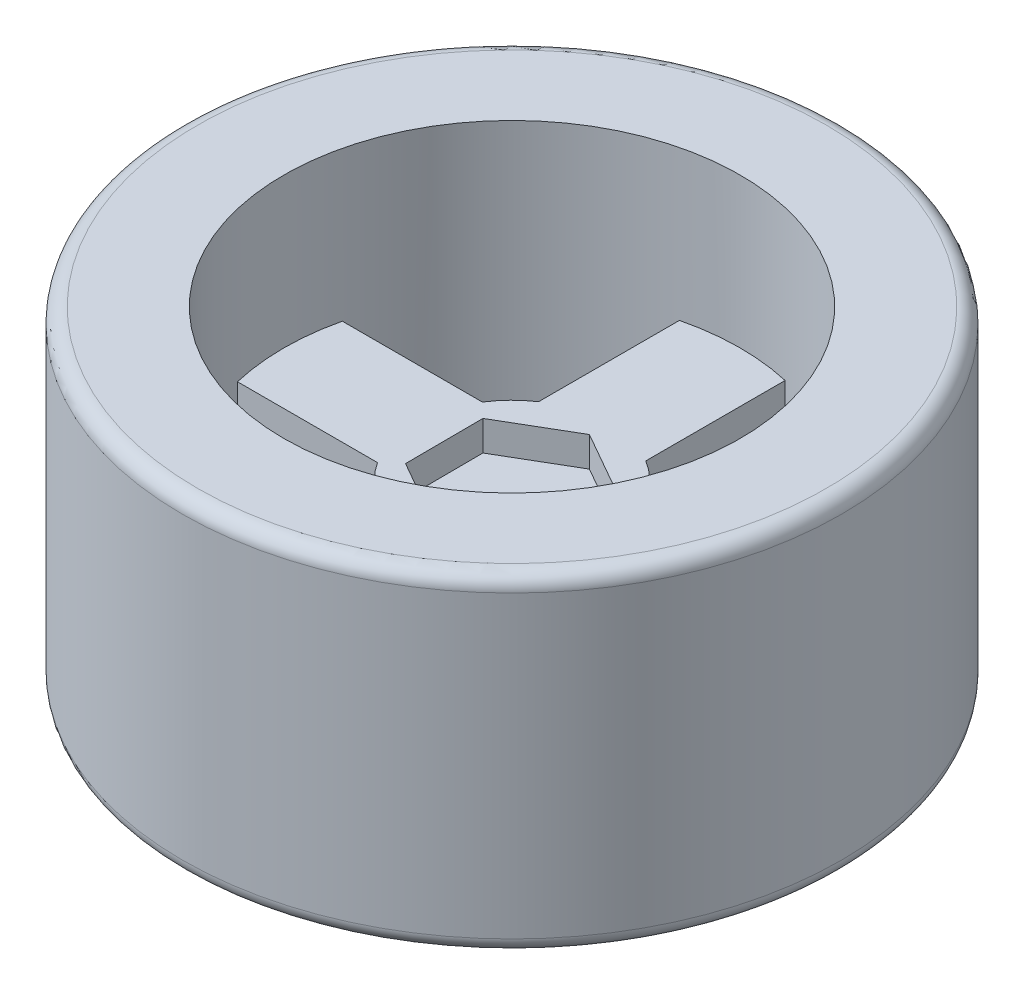
SolidWorks part; units mm, degrees
ref_plane "Front Plane" through (0, 0, 0) normal (0, 0, 1) x (1, 0, 0)
ref_plane "Top Plane" through (0, 0, 0) normal (0, 1, 0) x (1, 0, 0)
ref_plane "Right Plane" through (0, 0, 0) normal (1, 0, 0) x (0, 0, -1)
sketch "Sketch1" plane through (0, 0, 0) normal (0, 1, 0) x (1, 0, 0)
  line L0 (-3.4277, 8.3858) -> (-3.4277, 17.6894)
  line L1 (-14.8781, 6.3326) -> (-5.5267, 6.3326)
  line L3 (-14.8781, -0.6674) -> (-5.5267, -0.6674)
  line L18 (3.5723, 8.2301) -> (3.5723, 17.6319)
  line L20 (5.4277, 6.3326) -> (14.779, 6.3326)
  line L22 (5.4277, -0.6674) -> (14.779, -0.6674)
  line L24 (-3.4277, -12.0242) -> (-3.4277, -2.7206)
  line L26 (3.5723, -11.9667) -> (3.5723, -2.5648)
  circle A0 centre (-0.0495, 2.8326) radius 22
  arc A1 (-3.4277, 8.3858) -> (-5.5267, 6.3326) centre (-0.0495, 2.8326) ccw
  circle A2 centre (-0.0495, 2.8326) radius 15.236
  arc A3 (5.4277, 6.3326) -> (3.5723, 8.2301) centre (-0.0495, 2.8326) ccw
  arc A4 (3.5723, -2.5648) -> (5.4277, -0.6674) centre (-0.0495, 2.8326) ccw
  arc A5 (-5.5267, -0.6674) -> (-3.4277, -2.7206) centre (-0.0495, 2.8326) ccw
  circle A6 centre (-0.0495, 2.8326) radius 1.7484
  dimension "D1" = 44
  dimension "D2" = 13
  dimension "D6" = 3.4968
  dimension "D3" = 0
  dimension "D4" = 3.5
  dimension "D5" = 3.5
  dimension "D9" = 0
extrude "Boss-Extrude2" add sketch "Sketch1" along normal blind 22 contours A0 A2 | A0 | A2 region at (-21.4273, 0, -2.8326)
ref_plane "Plane3" through (0, 0, 0) normal (0, -1, 0) x (-1, 0, 0)
ref_point "Point2"
sketch "Sketch3" plane through (0, 0, 0) normal (0, -1, 0) x (-1, 0, 0)
  line L0 (-3.3287, 8.3858) -> (-3.3287, 17.6894)
  line L1 (-14.779, 6.3326) -> (-5.4277, 6.3326)
  line L2 (-14.779, -0.6674) -> (-5.4277, -0.6674)
  line L3 (3.6713, 8.2301) -> (3.6713, 17.6319)
  line L4 (5.5267, 6.3326) -> (14.8781, 6.3326)
  line L5 (5.5267, -0.6674) -> (14.8781, -0.6674)
  line L6 (-3.3287, -12.0242) -> (-3.3287, -2.7206)
  line L7 (3.6713, -11.9667) -> (3.6713, -2.5648)
  arc A0 (-3.3287, 8.3858) -> (-5.4277, 6.3326) centre (0.0495, 2.8326) ccw
  circle A1 centre (0.0495, 2.8326) radius 15.236
  arc A2 (5.5267, 6.3326) -> (3.6713, 8.2301) centre (0.0495, 2.8326) ccw
  arc A3 (3.6713, -2.5648) -> (5.5267, -0.6674) centre (0.0495, 2.8326) ccw
  arc A4 (-5.4277, -0.6674) -> (-3.3287, -2.7206) centre (0.0495, 2.8326) ccw
  circle A5 centre (0.0495, 2.8326) radius 1.5
extrude "Boss-Extrude3" add sketch "Sketch3" against normal blind 12 contours L2 A4 L6 A1 L7 A3 L5 L4 A2 L3 L0 A0 L1 A5 region at (2.8977, 0, -13.0376)
ref_plane "Plane4" through (0, 0, 0) normal (0, -1, 0) x (-1, 0, 0)
sketch "Sketch4" plane through (0, 0, 0) normal (0, -1, 0) x (-1, 0, 0)
  circle A0 centre (0.0495, 2.8326) radius 4.9908
extrude "Cut-Extrude1" cut sketch "Sketch4" against normal blind 6
ref_plane "Plane5" through (0, 12, 0) normal (0, 1, 0) x (1, 0, 0)
sketch "Sketch5" plane through (0, 12, 0) normal (0, 1, 0) x (1, 0, 0)
  line L1 (-4.5635, 5.4064) -> (-4.5354, 0.2103)
  line L2 (-4.5354, 0.2103) -> (-0.0215, -2.3635)
  line L3 (-0.0215, -2.3635) -> (4.4644, 0.2589)
  line L4 (4.4644, 0.2589) -> (4.4364, 5.4549)
  line L5 (4.4364, 5.4549) -> (-0.0776, 8.0287)
  line L6 (-0.0776, 8.0287) -> (-4.5635, 5.4064)
  circle A0 centre (-0.0495, 2.8326) radius 4.5 construction
  dimension "D1" = 9
extrude "Cut-Extrude2" cut sketch "Sketch5" against normal blind 2
fillet "Fillet1" radius 1 1 edges at (-0.0495, 22, 19.1674)
fillet "Fillet2" radius 1 1 edges at (-0.0495, 0, 19.1674)
